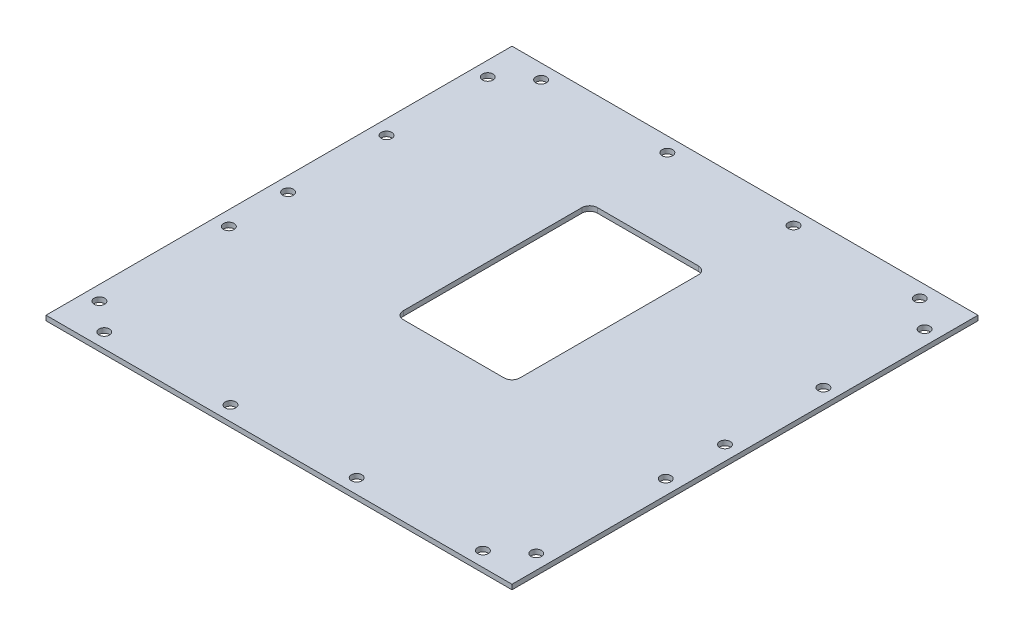
SolidWorks part; units mm, degrees
ref_plane "Front Plane" through (0, 0, 0) normal (0, 0, 1) x (1, 0, 0)
ref_plane "Top Plane" through (0, 0, 0) normal (0, 1, 0) x (1, 0, 0)
ref_plane "Right Plane" through (0, 0, 0) normal (1, 0, 0) x (0, 0, -1)
sketch "Sketch2" plane through (0, 0, 0) normal (0, 1, 0) x (1, 0, 0)
  line L0 (0, 0) -> (152.4, 0)
  line L1 (152.4, 0) -> (152.4, 152.4)
  line L2 (152.4, 152.4) -> (0, 152.4)
  line L3 (0, 152.4) -> (0, 0)
  dimension "D1" = 152.4
  dimension "D2" = 152.4
extrude "Boss-Extrude1" add sketch "Sketch2" along normal blind 1.5875
sketch "Sketch3" plane through (0, 1.5875, 0) normal (0, 1, 0) x (1, 0, 0)
  line L0 (0, 152.4) -> (4.7625, 152.4)
  line L1 (152.4, 152.4) -> (0, 152.4) construction
  line L2 (4.7625, 152.4) -> (4.7625, 0)
  line L3 (0, 0) -> (152.4, 0) construction
  line L4 (0, 152.4) -> (0, 147.6375)
  line L5 (0, 152.4) -> (0, 0) construction
  line L6 (0, 147.6375) -> (152.4, 147.6375)
  line L7 (152.4, 0) -> (152.4, 152.4) construction
  line L8 (152.4, 152.4) -> (147.6375, 152.4)
  line L9 (147.6375, 152.4) -> (147.6375, 0)
  line L10 (152.4, 0) -> (152.4, 4.7625)
  line L11 (152.4, 4.7625) -> (0, 4.7625)
  point P21 (4.7625, 139.7)
  point P23 (14.2875, 147.6375)
  point P24 (147.6375, 139.7)
  point P25 (138.1125, 4.7625)
  point P26 (4.7625, 12.7)
  dimension "D1" = 4.7625
  dimension "D2" = 4.7625
  dimension "D3" = 4.7625
  dimension "D4" = 4.7625
  dimension "D5" = 12.7
  dimension "D6" = 14.2875
  dimension "D7" = 12.7
  dimension "D8" = 14.2875
  dimension "D9" = 12.7
sketch "Sketch4" plane through (0, 1.5875, 0) normal (0, 1, 0) x (1, 0, 0)
  point P0 (14.2875, 147.6375)
  point P3 (147.6375, 139.7)
  point P6 (138.1125, 4.7625)
  point P9 (4.7625, 12.7)
sketch "Sketch6" plane through (0, 1.5875, 0) normal (0, 1, 0) x (1, 0, 0)
  line L0 (152.4, 4.7625) -> (0, 4.7625) construction
  line L1 (0, 152.4) -> (0, 0) construction
  point P0 (14.2875, 147.6375)
  point P3 (14.2875, 4.7625)
  dimension "D1" = 14.2875
hole_wizard "#5 Clearance Hole2" positions "Sketch6" profile "Sketch7" hole size "#5" standard "ANSI Inch" end condition through all
sketch "Sketch7" plane through (14.2875, 1.5875, -147.6375) normal (1, 0, 0) x (0, 0, 1)
  line L0 (0, 0) -> (0, 1.5875)
  line L1 (0, 1.5875) -> (1.7272, 1.5875)
  line L2 (1.7272, 1.5875) -> (1.7272, 0)
  line L5 (1.7272, 0) -> (0, 0)
  line L11 (0, -6.35) -> (0, 107.95) construction
  dimension "Thru Hole Dia." = 3.4544
  dimension "Thru Hole Depth" = 1.5875
sketch "Sketch8" plane through (0, 1.5875, 0) normal (0, 1, 0) x (1, 0, 0)
  point P0 (4.7625, 139.7)
  point P3 (147.6375, 139.7)
hole_wizard "#5 Clearance Hole3" positions "Sketch8" profile "Sketch9" hole size "#5" standard "ANSI Inch" end condition through all
sketch "Sketch9" plane through (4.7625, 1.5875, -139.7) normal (1, 0, 0) x (0, 0, 1)
  line L0 (0, 0) -> (0, 1.5875)
  line L1 (0, 1.5875) -> (1.7272, 1.5875)
  line L2 (1.7272, 1.5875) -> (1.7272, 0)
  line L5 (1.7272, 0) -> (0, 0)
  line L11 (0, -6.35) -> (0, 107.95) construction
  dimension "Thru Hole Dia." = 3.4544
  dimension "Thru Hole Depth" = 1.5875
pattern_linear "LPattern1" count 4 spacing 42.3333 along (0, 0, 1) skipping (1, 0) of "#5 Clearance Hole3"
pattern_linear "LPattern2" count 4 spacing 41.275 along (1, 0, 0) of "#5 Clearance Hole2"
sketch "Sketch10" plane through (0, 1.5875, 0) normal (0, 1, 0) x (1, 0, 0)
  line L0 (152.4, 0) -> (152.4, 152.4) construction
  line L1 (152.4, 152.4) -> (0, 152.4) construction
  line L2 (76.2, 152.4) -> (76.2, 0) construction
  line L3 (0, 0) -> (152.4, 0) construction
  point P0 (147.6375, 106.61)
  point P5 (147.6375, 74.4)
  point P10 (4.7625, 74.4)
  point P11 (4.7625, 106.61)
  point P12 (0, 0)
  dimension "D1" = 4.7625
  dimension "D2" = 78
  dimension "D3" = 32.21
hole_wizard "#5 Clearance Hole4" positions "Sketch10" profile "Sketch11" hole size "#5" standard "ANSI Inch"
sketch "Sketch11" plane through (147.6375, 1.5875, -106.61) normal (1, 0, 0) x (0, 0, 1)
  line L0 (0, 0) -> (0, 13.7378)
  line L1 (0, 13.7378) -> (1.7272, 12.7)
  line L2 (1.7272, 12.7) -> (1.7272, 0)
  line L5 (1.7272, 0) -> (0, 0)
  line L10 (0, 13.7378) -> (-1.7272, 12.7) construction
  line L11 (0, -6.35) -> (0, 107.95) construction
  dimension "Hole Dia." = 3.4544
  dimension "Hole Depth" = 12.7
  dimension "Drill Angle" = 118
sketch "Sketch12" plane through (0, 1.5875, 0) normal (0, 1, 0) x (1, 0, 0)
  line L10 (0, 152.4) -> (0, 0) construction
  line L11 (57.15, 120.65) -> (95.25, 120.65)
  line L12 (57.15, 120.65) -> (57.15, 57.15)
  line L13 (57.15, 57.15) -> (95.25, 57.15)
  line L14 (95.25, 120.65) -> (95.25, 57.15)
  line L15 (152.4, 152.4) -> (0, 152.4) construction
  line L16 (152.4, 0) -> (152.4, 152.4) construction
  dimension "D1" = 57.15
  dimension "D2" = 31.75
  dimension "D3" = 57.15
  dimension "D4" = 63.5
extrude "Cut-Extrude1" cut sketch "Sketch12" against normal blind 2.54 contours L14 L12 region at (76.2, 1.5875, -88.9)
fillet "Fillet2" radius 2.54 4 edges at (95.25, 0.7937, -57.15) (57.15, 0.7937, -57.15) (57.15, 0.7937, -120.65) (95.25, 0.7937, -120.65)
